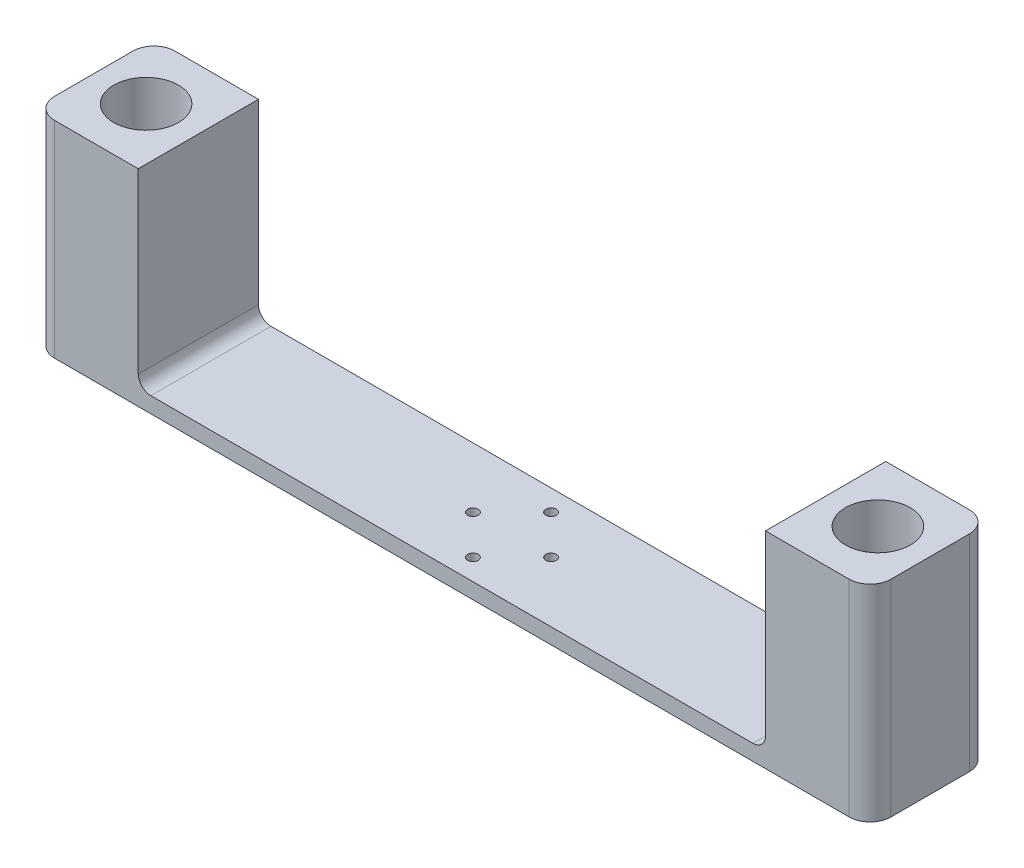
SolidWorks part; units mm, degrees
ref_plane "Front Plane" through (0, 0, 0) normal (0, 0, 1) x (1, 0, 0)
ref_plane "Top Plane" through (0, 0, 0) normal (0, 1, 0) x (1, 0, 0)
ref_plane "Right Plane" through (0, 0, 0) normal (1, 0, 0) x (0, 0, -1)
sketch "Sketch1" plane through (0, 0, 0) normal (0, 1, 0) x (1, 0, 0)
  line L0 (0, 0) -> (0, 4.9523) construction
  line L1 (0, 4.9523) -> (0, 0) construction
  line L2 (0, 0) -> (2.8355, 0) construction
  circle A0 centre (0, 0) radius 13.97
  circle A2 centre (0, 9.5) radius 1.275
  circle A3 centre (9.5, 0) radius 1.275
  circle A4 centre (0, -9.5) radius 1.275
  circle A5 centre (-9.5, 0) radius 1.275
  dimension "D2" = 27.94
  dimension "D3" = 2.55
extrude "Boss-Extrude1" add sketch "Sketch1" along normal blind 3.048
sketch "Sketch2" plane through (0, 3.048, 0) normal (0, 1, 0) x (1, 0, 0)
  line L1 (-96.52, -14.605) -> (96.52, -14.605)
  line L2 (-101.6, -9.525) -> (-101.6, 9.525)
  line L3 (-96.52, 14.605) -> (96.52, 14.605)
  line L4 (101.6, -9.525) -> (101.6, 9.525)
  line L5 (-101.6, -14.605) -> (101.6, 14.605) construction
  line L6 (-101.6, 14.605) -> (101.6, -14.605) construction
  circle A0 centre (-88.9, 0) radius 7.874
  circle A1 centre (88.9, 0) radius 7.874
  arc A3 (96.52, 14.605) -> (101.6, 9.525) centre (96.52, 9.525) cw
  arc A4 (96.52, -14.605) -> (101.6, -9.525) centre (96.52, -9.525) ccw
  arc A5 (-96.52, -14.605) -> (-101.6, -9.525) centre (-96.52, -9.525) cw
  arc A6 (-101.6, 9.525) -> (-96.52, 14.605) centre (-96.52, 9.525) cw
  circle A7 centre (9.5, 0) radius 1.275 construction
  circle A8 centre (0, 9.5) radius 1.275 construction
  circle A9 centre (-9.5, 0) radius 1.275 construction
  circle A10 centre (0, -9.5) radius 1.275 construction
  circle A11 centre (9.5, 0) radius 1.275
  circle A12 centre (0, 9.5) radius 1.275
  circle A13 centre (-9.5, 0) radius 1.275
  circle A14 centre (0, -9.5) radius 1.275
  point P0 (0, 0)
  dimension "D2" = 15.748
  dimension "D3" = 15.748
  dimension "D8" = 5.08
  dimension "D1" = 29.21
  dimension "D4" = 88.9
  dimension "D6" = 12.7
  dimension "D7" = 12.7
extrude "Boss-Extrude2" add sketch "Sketch2" along normal blind 46.99 and the other way through all
sketch "Sketch5" plane through (0, 0, -14.605) normal (0, 0, -1) x (-1, 0, 0)
  line L0 (-101.6, 0) -> (-101.6, 50.038)
  line L1 (-101.6, 50.038) -> (-76.2, 50.038)
  line L2 (-96.52, 50.038) -> (96.52, 50.038) construction
  line L3 (-76.2, 50.038) -> (-76.2, 3.81)
  line L4 (-76.2, 3.81) -> (76.2, 3.81)
  line L5 (0, 3.81) -> (0, 0)
  line L6 (101.6, 0) -> (-101.6, 0)
  line L7 (76.2, 50.038) -> (76.2, 3.81)
  line L8 (101.6, 50.038) -> (76.2, 50.038)
  line L9 (101.6, 0) -> (101.6, 50.038)
  line M8 (96.52, 50.038) -> (-96.52, 50.038)
  dimension "D1" = 25.4
  dimension "D2" = 3.81
extrude "Cut-Extrude2" cut sketch "Sketch5" against normal through all contours L7 L3 L4 M8 region at (0, 26.924, -14.605)
sketch "Sketch6" plane through (0, 0, 0) normal (0, -1, 0) x (1, 0, 0)
  circle A0 centre (-88.9, 0) radius 8.89
  circle A1 centre (-88.9, 0) radius 4.191
  circle A2 centre (88.9, 0) radius 8.89
  circle A3 centre (88.9, 0) radius 4.191
  dimension "D1" = 8.382
  dimension "D2" = 8.382
extrude "Boss-Extrude3" add sketch "Sketch6" against normal blind 4.572
fillet "Fillet2" radius 3.048 2 edges at (76.2, 3.81, 0) (-76.2, 3.81, 0)
